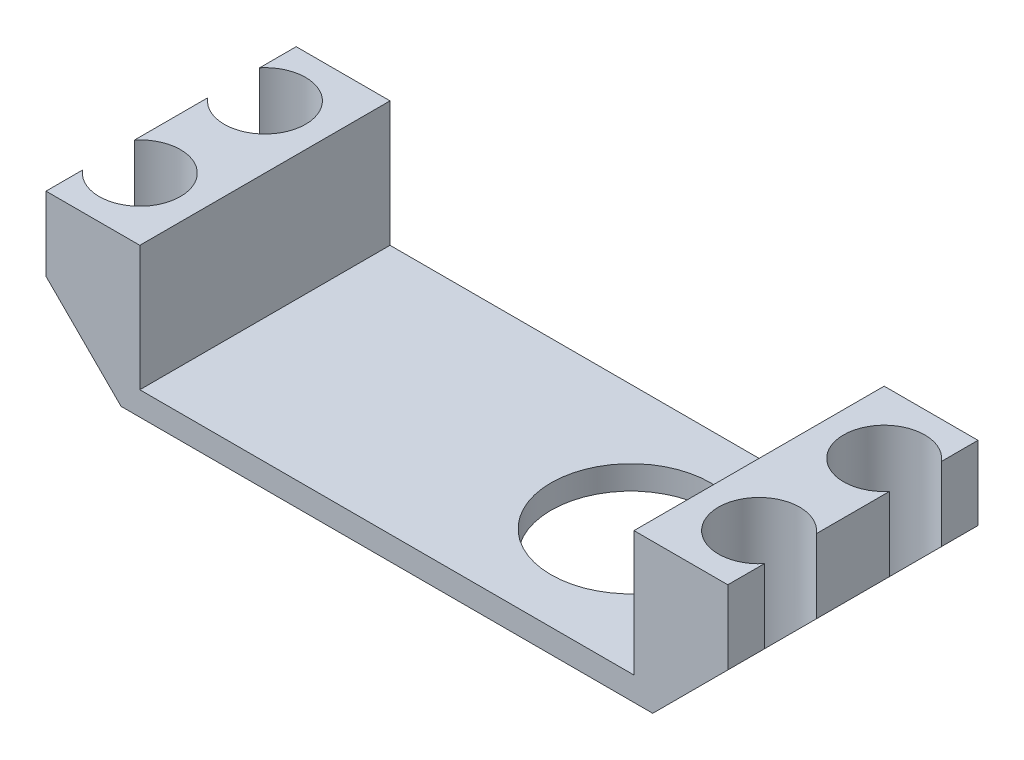
SolidWorks part; units mm, degrees
ref_plane "Front Plane" through (0, 0, 0) normal (0, 0, 1) x (1, 0, 0)
ref_plane "Top Plane" through (0, 0, 0) normal (0, 1, 0) x (1, 0, 0)
ref_plane "Right Plane" through (0, 0, 0) normal (1, 0, 0) x (0, 0, -1)
sketch "Sketch1" plane through (0, 0, 0) normal (0, 0, 1) x (1, 0, 0)
  line L0 (-27.25, 1) -> (-27.25, 10.9)
  line L1 (-19.75, 0.9) -> (19.75, 0.9)
  line L2 (-27.25, 1) -> (-27.25, -1)
  line L3 (-27.25, -1) -> (27.25, -1)
  line L4 (27.25, 1) -> (27.25, -1)
  line L5 (-27.25, 1) -> (27.25, -1) construction
  line L6 (-27.25, -1) -> (27.25, 1) construction
  line L7 (-27.25, 10.9) -> (-19.75, 10.9)
  line L8 (-19.75, 10.9) -> (-19.75, 0.9)
  line L9 (27.25, 1) -> (27.25, 10.9)
  line L10 (27.25, 10.9) -> (19.75, 10.9)
  line L11 (19.75, 10.9) -> (19.75, 0.9)
  point P0 (0, 0)
  dimension "D1" = 54.5
  dimension "D2" = 2
  dimension "D3" = 9.9
  dimension "D4" = 7.5
  dimension "D5" = 7.5
  dimension "D6" = 9.9
extrude "Boss-Extrude1" add sketch "Sketch1" along normal blind 20
sketch "Sketch2" plane through (0, 0, 0) normal (0, 1, 0) x (1, 0, 0)
  line L0 (-19.75, -20) -> (-19.75, 0) construction
  line L1 (-19.75, 0) -> (-27.25, 0) construction
  line L2 (0, 8.7578) -> (0, -25.7221) construction
  line L3 (-27.25, -10) -> (27.25, -10) construction
  line L4 (-27.25, -20) -> (-27.25, 0) construction
  line L5 (27.25, -20) -> (27.25, 0) construction
  circle A0 centre (-24.75, -5) radius 3.25
  circle A1 centre (24.75, -5) radius 3.25
  circle A2 centre (24.75, -15) radius 3.25
  circle A3 centre (-24.75, -15) radius 3.25
  dimension "D1" = 6.5
  dimension "D2" = 5
  dimension "D3" = 5
extrude "Cut-Extrude2" cut sketch "Sketch2" against normal through all both and the other way through all
chamfer "Chamfer1" distance 6 angle 45 5 edges at (-27.25, -1, 1.4617) (-27.25, -1, 10) (27.25, -1, 1.4617) (27.25, -1, 10) (27.25, -1, 18.5383)
sketch "Sketch3" plane through (0, 0, 0) normal (0, 1, 0) x (1, 0, 0)
  line L0 (19.75, -20) -> (19.75, 0) construction
  circle A0 centre (9.5, -10) radius 6.375
  dimension "D1" = 10.25
  dimension "D2" = 12.75
extrude "Cut-Extrude3" cut sketch "Sketch3" against normal through all both and the other way through all
sketch "Sketch5" plane through (0, 0, 0) normal (0, 0, 1) x (1, 0, 0)
  line L0 (27.25, -1) -> (35, -1)
  line L4 (35, -1) -> (42.6796, 6.6164) construction
  line L5 (42.6796, 6.6164) -> (42.6796, 17.2632) construction
  line L6 (27.25, 1.5) -> (33.9445, 1.5)
  line L7 (40.1796, 17.2632) -> (42.6796, 17.2632)
  line L8 (27.25, 1.5) -> (27.25, -1)
  line L9 (0, 0) -> (0, 17.8091) construction
  line L10 (0, 1.5) -> (33.9445, 1.5) construction
  line L11 (0, -1) -> (35, -1) construction
  line L12 (0, 0) -> (20.8227, 0) construction
  spline S0 degree 2 poles (35, -1) (42.6796, 6.6164) (42.6796, 17.2632) knots 0 0 0 1 1 1
  spline S1 degree 1 poles (33.9445, 1.5) (40.1796, 17.2632) knots 0 0 1 1 construction
  spline S2 degree 2 poles (33.9445, 1.5) (36.3085, 4.028) (38.7233, 8.7265) (40.1754, 13.8046) (40.1796, 17.2632) knots 0.051356 0.051356 0.051356 0.407097 0.644258 1 1 1
  dimension "D2" = 2.5
